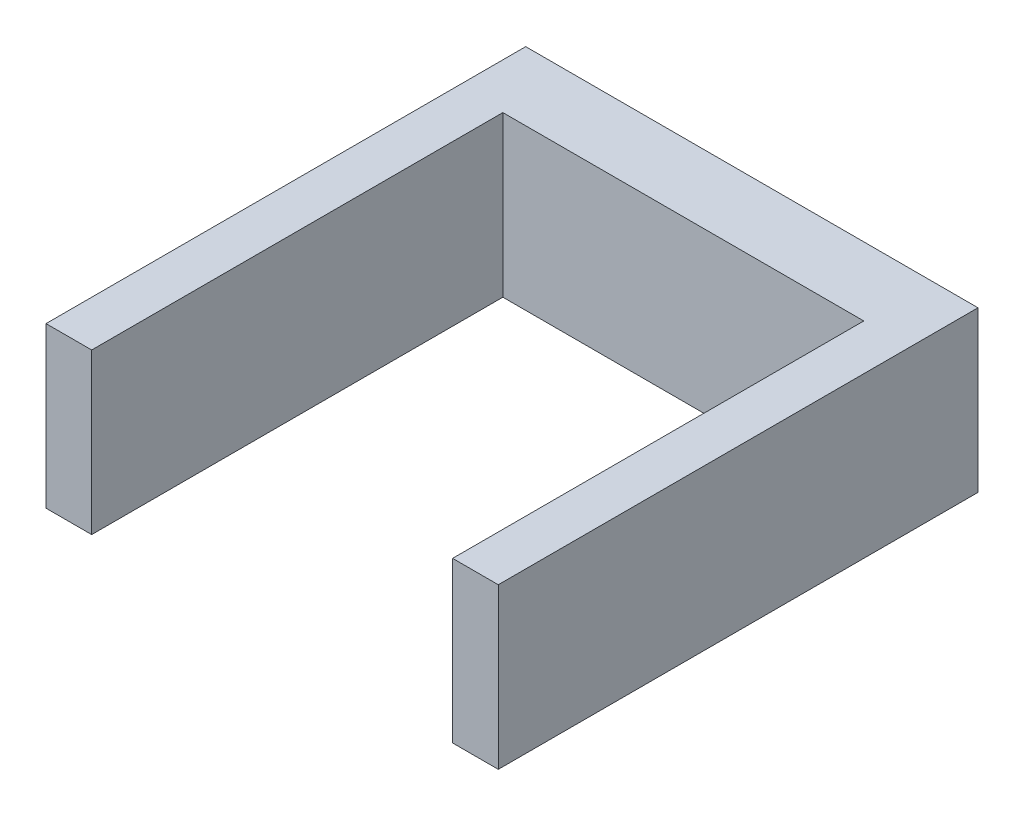
SolidWorks part; units mm, degrees
ref_plane "Front Plane" through (0, 0, 0) normal (0, 0, 1) x (1, 0, 0)
ref_plane "Top Plane" through (0, 0, 0) normal (0, 1, 0) x (1, 0, 0)
ref_plane "Right Plane" through (0, 0, 0) normal (1, 0, 0) x (0, 0, -1)
sketch "Sketch1" plane through (0, 0, 0) normal (0, 1, 0) x (1, 0, 0)
  line L0 (4.126, 9.3185) -> (4.126, 50009.3185) construction
  line L1 (-5.774, 12.3185) -> (14.026, 12.3185) construction
  line L2 (-5.774, 12.3185) -> (-5.774, 9.3185) construction
  line L3 (-5.774, 9.3185) -> (14.026, 9.3185) construction
  line L4 (14.026, 12.3185) -> (14.026, 9.3185) construction
  line L6 (-5.774, 9.3185) -> (-5.774, -8.6815) construction
  line L7 (-5.774, -8.6815) -> (-3.774, -8.6815) construction
  line L8 (-3.774, 9.3185) -> (-3.774, -8.6815) construction
  line L9 (14.026, -8.6815) -> (12.026, -8.6815) construction
  line L10 (12.026, 9.3185) -> (12.026, -8.6815) construction
  line L12 (14.026, 9.3185) -> (14.026, -8.6815) construction
  line L13 (-5.774, 12.3185) -> (-5.774, -8.6815)
  line L14 (-5.774, -8.6815) -> (-3.774, -8.6815)
  line L15 (-3.774, -8.6815) -> (-3.774, 9.3185)
  line L16 (-3.774, 9.3185) -> (12.026, 9.3185)
  line L17 (12.026, 9.3185) -> (12.026, -8.6815)
  line L18 (12.026, -8.6815) -> (14.026, -8.6815)
  line L19 (14.026, -8.6815) -> (14.026, 12.3185)
  line L20 (14.026, 12.3185) -> (-5.774, 12.3185)
  point P9 (4.126, 9.3185)
  dimension "D1" = 3
  dimension "D2" = 19.8
  dimension "D3" = 18
  dimension "D4" = 2
extrude "Boss-Extrude1" add sketch "Sketch1" along normal blind 7
